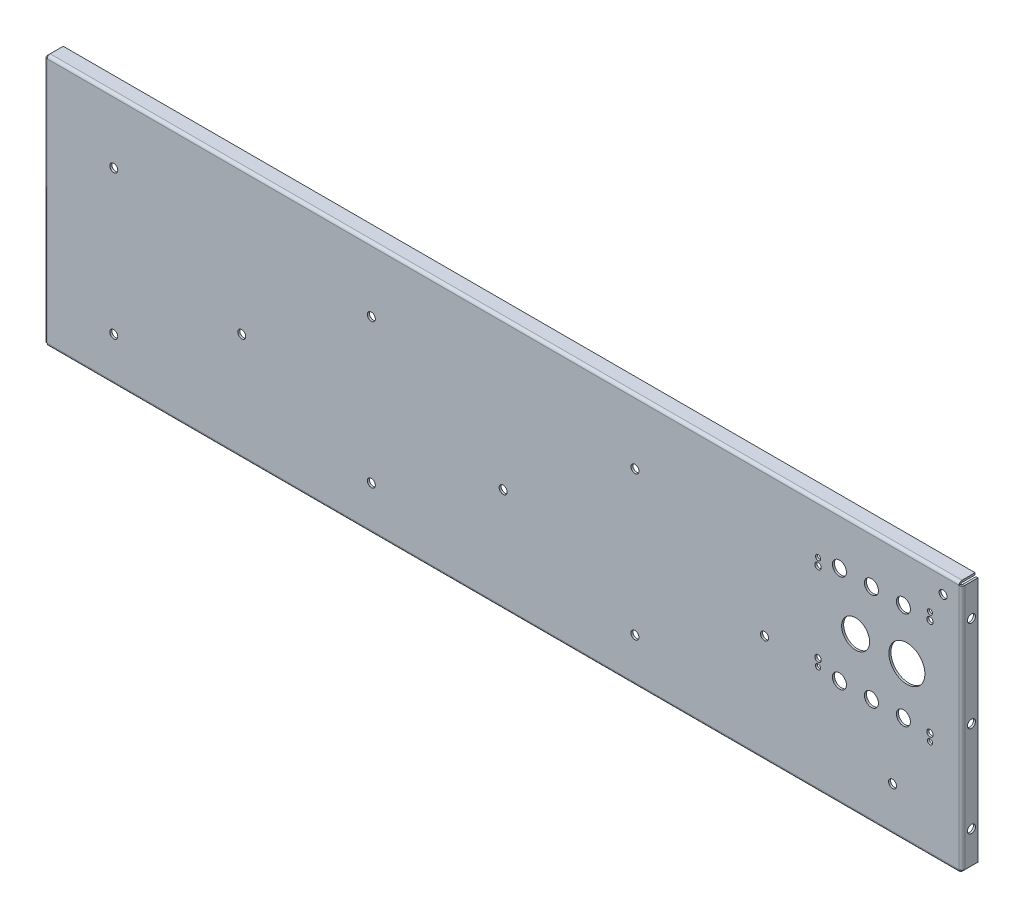
SolidWorks part; units mm, degrees
note: '?' marks a value the reader was unsure of. The reader was unsure of these and kept them because the rebuilt part matched: flange length of "Edge-Flange1", "Edge-Flange2", "Edge-Flange3".
ref_plane "Front Plane" through (0, 0, 0) normal (0, 0, 1) x (1, 0, 0)
ref_plane "Top Plane" through (0, 0, 0) normal (0, 1, 0) x (1, 0, 0)
ref_plane "Right Plane" through (0, 0, 0) normal (1, 0, 0) x (0, 0, -1)
sketch "Sketch1" plane through (0, 0, 0) normal (0, 0, 1) x (1, 0, 0)
  line L1 (-361.95, -100.076) -> (361.95, -100.076)
  line L2 (-361.95, -100.076) -> (-361.95, 100.076)
  line L3 (-361.95, 100.076) -> (361.95, 100.076)
  line L4 (361.95, -100.076) -> (361.95, 100.076)
  line L5 (-361.95, -100.076) -> (361.95, 100.076) construction
  line L6 (-361.95, 100.076) -> (361.95, -100.076) construction
  point P0 (0, 0)
  dimension "D1" = 200.152
  dimension "D2" = 723.9
base flange "Base-Flange1" sketch "Sketch1" thickness 1.6002 reverse thickness direction no parameters "D1"=0.7366
edge flange "Edge-Flange1" sketch "Sketch8" flange angle 90 flange length 12.7 flange position material inside bend radius 0.7366 thickness 1.6002 relief rectangular parameters "D6"=10
sketch "Sketch8" plane through (0, 100.076, -1.6002) normal (0, -1, 0) x (-1, 0, 0)
  line L1 (361.95, 0) -> (-361.95, 0) construction
  line L2 (-361.95, 0) -> (-361.95, 11.0998)
  line L3 (-361.95, 11.0998) -> (361.95, 11.0998)
  line L4 (361.95, 11.0998) -> (361.95, 0)
  line L5 (361.95, 0) -> (-361.95, 0)
bend "EdgeBend1" bend radius 0.7366 bend angle 90 parameters "D5"=1
edge flange "Edge-Flange2" sketch "Sketch11" flange angle 90 flange length 12.7 flange position material inside bend radius 0.7366 thickness 1.6002 relief rectangular parameters "D6"=10
sketch "Sketch11" plane through (0, -100.076, -1.6002) normal (0, -1, 0) x (-1, 0, 0)
  line L1 (361.95, 0) -> (-361.95, 0) construction
  line L2 (-361.95, 0) -> (-361.95, 11.0998)
  line L3 (-361.95, 11.0998) -> (361.95, 11.0998)
  line L4 (361.95, 11.0998) -> (361.95, 0)
  line L6 (361.95, 0) -> (-361.95, 0)
bend "EdgeBend2" bend radius 0.7366 bend angle 90 parameters "D5"=2
sketch "Sketch12" plane through (0, 0, -1.6002) normal (0, 0, -1) x (-1, 0, 0)
  line L0 (-320.548, 23.2684) -> (-361.95, 23.2684) construction
  line L1 (-361.95, -97.7392) -> (-361.95, 97.7392) construction
  line L2 (-320.548, 23.2684) -> (-207.518, -14.351) construction
  circle A0 centre (-207.518, -14.351) radius 3.175
  circle A1 centre (0, -17.526) radius 3.175
  circle A2 centre (207.518, -14.351) radius 3.175
  circle A3 centre (-207.518, -14.351) radius 3.175 construction
  circle A4 centre (-320.548, 23.2684) radius 20.955 construction
  circle A5 centre (-320.548, 23.2684) radius 14.2875
  circle A21 centre (-207.518, -14.351) radius 101.6 construction
  circle A22 centre (0, -17.526) radius 101.6 construction
  circle A23 centre (207.518, -14.351) radius 101.6 construction
  dimension "D1" = 41.91
  dimension "D24" = 203.2
  dimension "D3" = 28.575
  dimension "D4" = 41.402
  dimension "D5" = 119.126
extrude "Cut-Extrude1" cut sketch "Sketch12" against normal through all normal cut yes
sketch "Sketch13" plane through (0, 0, -108.3564) normal (0, 0, -1) x (-1, 0, 0)
  circle A1 centre (-309.118, -65.151) radius 3.175
  circle A2 centre (-104.6381, -65.151) radius 3.175
  circle A3 centre (-104.6381, 49.149) radius 3.175
  circle A4 centre (104.6381, 49.149) radius 3.175
  circle A5 centre (104.6381, -65.151) radius 3.175
  circle A6 centre (309.118, -65.151) radius 3.175
  circle A7 centre (309.118, 49.149) radius 3.175
extrude "Cut-Extrude2" cut sketch "Sketch13" against normal through all normal cut yes
edge flange "Edge-Flange3" sketch "Sketch18" flange profiles "Sketch18", "Sketch19" flange angle 90 flange length 12.7 flange position bend outside bend radius 0.7366 thickness 1.6002 relief rectangular parameters "D6"=10, "D8"=0.254
sketch "Sketch18" plane through (-361.95, 0, -1.6002) normal (-1, 0, 0) x (0, 1, 0)
  line L1 (97.7392, 0) -> (-97.7392, 0) construction
  line L2 (-97.7392, 0) -> (-97.7392, 11.0998)
  line L3 (-97.7392, 11.0998) -> (97.7392, 11.0998)
  line L4 (97.7392, 11.0998) -> (97.7392, 0)
  line L5 (97.7392, 0) -> (-97.7392, 0)
sketch "Sketch19" plane through (361.95, 0, -1.6002) normal (1, 0, 0) x (0, -1, 0)
  line L2 (-97.7392, 0) -> (-97.7392, 11.0998)
  line L3 (-97.7392, 11.0998) -> (97.7392, 11.0998)
  line L4 (97.7392, 11.0998) -> (97.7392, 0)
  line L5 (97.7392, 0) -> (-97.7392, 0) construction
  line L6 (97.7392, 0) -> (-97.7392, 0)
bend "EdgeBend3" bend radius 0.7366 bend angle 90 parameters "D5"=3
bend "EdgeBend4" bend radius 0.7366 bend angle 90 parameters "D5"=4
sketch "Sketch20" plane through (-364.2868, 0, 0) normal (-1, 0, 0) x (0, 0, 1)
  line L1 (-7.5184, 97.7392) -> (-7.5184, -97.7392) construction
  line L2 (-2.3368, 97.7392) -> (-12.7, 97.7392) construction
  line L3 (-12.7, -97.7392) -> (-2.3368, -97.7392) construction
  circle A0 centre (-7.5184, 72.3392) radius 3.175
  circle A1 centre (-7.5184, 0) radius 3.175
  circle A2 centre (-7.5184, -72.3392) radius 3.175
  point P14 (-7.5184, 0)
  dimension "D1" = 6.35
  dimension "D2" = 25.4
  dimension "D3" = 25.4
extrude "Cut-Extrude3" cut sketch "Sketch20" against normal through all normal cut yes
sketch "Sketch22" plane through (0, 0, 0) normal (0, 0, 1) x (1, 0, 0)
  line L0 (279.8318, 23.2684) -> (320.548, 23.2684) construction
  line L1 (338.8601, -21.3086) -> (338.8601, -15.4666) construction
  line L2 (338.8601, 62.0034) -> (338.8601, 67.8454) construction
  line L3 (320.548, 23.2684) -> (338.8601, 62.0034) construction
  line L4 (320.548, 23.2684) -> (338.8601, -15.4666) construction
  line L5 (320.548, 23.2684) -> (317.7781, -15.4666) construction
  line L6 (320.548, 23.2684) -> (317.7781, 62.0034) construction
  line L7 (279.8318, 23.2684) -> (292.3781, 62.0034) construction
  line L8 (279.8318, 23.2684) -> (266.9781, 62.0034) construction
  line L9 (279.8318, 23.2684) -> (266.9781, -15.4666) construction
  line L10 (279.8318, 23.2684) -> (292.3781, -15.4666) construction
  line L11 (279.8318, 23.2684) -> (249.9601, -8.4816) construction
  line L12 (249.9601, -14.3236) -> (249.9601, -8.4816) construction
  line L13 (279.8318, 23.2684) -> (249.9601, 55.0184) construction
  line L14 (249.9601, 55.0184) -> (249.9601, 60.8604) construction
  circle A0 centre (279.8318, 23.2684) radius 21 construction
  circle A1 centre (266.9781, -15.4666) radius 5.5562
  circle A2 centre (249.9601, -8.4816) radius 2.5527
  circle A3 centre (249.9601, -14.3236) radius 2.0447
  circle A4 centre (249.9601, 55.0184) radius 2.5527
  circle A5 centre (249.9601, 60.8604) radius 2.0447
  circle A6 centre (266.9781, 62.0034) radius 5.5562
  circle A7 centre (292.3781, 62.0034) radius 5.5563
  circle A8 centre (317.7781, 62.0034) radius 5.5563
  circle A9 centre (338.8601, 62.0034) radius 2.5527
  circle A10 centre (338.8601, 67.8454) radius 2.0447
  circle A11 centre (338.8601, -15.4666) radius 2.5527
  circle A12 centre (338.8601, -21.3086) radius 2.0447
  circle A13 centre (320.548, 23.2684) radius 14.2812 construction
  circle A14 centre (279.8318, 23.2684) radius 11.1061
  circle A15 centre (292.3781, -15.4666) radius 5.5562
  circle A16 centre (317.7781, -15.4666) radius 5.5562
  circle A17 centre (320.548, 23.2684) radius 21 construction
  circle A18 centre (320.548, 23.2684) radius 14.2875 construction
  point P0 (203.3448, 316.475)
  dimension "D15" = 11.1125
  dimension "D17" = 4.0894
  dimension "D19" = 28.5623
  dimension "D1" = 43.5934
  dimension "D2" = 46.746
  dimension "D3" = 5.842
  dimension "D4" = 136.746
  dimension "D5" = 46.746
  dimension "D6" = 24.896
  dimension "D7" = 36.305
  dimension "D8" = 36.305
  dimension "D9" = 24.896
  dimension "D10" = 40.812
  dimension "D11" = 85.91
  dimension "D12" = 85.91
  dimension "D13" = 29.393
  dimension "D14" = 29.393
  dimension "D16" = 38.8339
  dimension "D18" = 5.842
  dimension "D20" = 154.697
  dimension "D21" = 154.697
  dimension "D22" = 136.746
  dimension "D23" = 40.7162
  dimension "D24" = 42.8454
  dimension "D25" = 40.7162
extrude "Cut-Extrude4" cut sketch "Sketch22" against normal through all normal cut yes
sketch "Sketch23" plane through (0, 0, -1.6002) normal (0, 0, -1) x (-1, 0, 0)
  line L5 (-361.95, 97.7392) -> (361.95, 97.7392) construction
  line L6 (-361.95, -97.7392) -> (-361.95, 97.7392) construction
  circle A0 centre (-349.25, 85.0392) radius 3.175
  dimension "D1" = 6.35
  dimension "D2" = 12.7
  dimension "D3" = 12.7
extrude "Cut-Extrude5" cut sketch "Sketch23" against normal through all normal cut yes
sketch "Bend-Lines1" [suppressed] plane through (0, 0, 0) normal (0, 1, 0) x (1, 0, 0)
sketch "Bounding-Box1" [suppressed] plane through (0, 0, 0) normal (0, 1, 0) x (1, 0, 0)
ref_axis "Axis1" [suppressed] through (400.7155, 0, 0) along (-1, 0, 0)?
sheet metal parameters "Sheet-Metal1" thickness 1.6002 parameters "D1"=0.7366
flat pattern "Flat-Pattern1" [suppressed]
sketch "Bend-Lines2" plane through (0, 0, 0) normal (0, 1, 0) x (1, 0, 0)
sketch3d "Bounding-Box2" [suppressed]
  line L0 (368.3, -100.076, 0) -> (-368.3, -100.076, 0) construction
  line L1 (368.3, 100.076, 0) -> (-368.3, 100.076, 0) construction
  line L2 (368.3, -100.076, 0) -> (368.3, 100.076, 0) construction
  line L3 (-368.3, -100.076, 0) -> (-368.3, 100.076, 0) construction
sheet metal parameters "Sheet-Metal2" thickness 1.6002 parameters "D1"=0.7366
flat pattern "Flat-Pattern1"
sketch "Bend-Lines2" plane through (0, 0, 0) normal (0, 0, 1) x (1, 0, 0)
  line L0 (368.3, 98.9461) -> (-368.3, 98.9461) construction
  line L1 (368.3, 98.9461) -> (-368.3, 98.9461) construction
sketch3d "Bounding-Box2" [suppressed]
  line L0 (-368.3, -100.076, 0) -> (368.3, -100.076, 0) construction
  line L1 (-368.3, 158.5222, 0) -> (368.3, 158.5222, 0) construction
  line L2 (-368.3, -100.076, 0) -> (-368.3, 158.5222, 0) construction
  line L3 (368.3, -100.076, 0) -> (368.3, 158.5222, 0) construction
bend of the flat pattern "Flatten-<EdgeBend1>1"
sheet metal parameters "Sheet-Metal3" thickness 1.6002 parameters "D1"=0.7366
flat pattern "Flat-Pattern1"
sketch "Bend-Lines2" plane through (0, 0, 0) normal (0, 0, 1) x (1, 0, 0)
  line L0 (368.3, 98.9461) -> (-368.3, 98.9461) construction
  line L1 (368.3, 98.9461) -> (-368.3, 98.9461) construction
  line L2 (-368.3, -98.9461) -> (368.3, -98.9461) construction
  line L3 (-368.3, -98.9461) -> (368.3, -98.9461) construction
sketch3d "Bounding-Box2" [suppressed]
  line L0 (-368.3, -110.5162, 0) -> (368.3, -110.5162, 0) construction
  line L1 (-368.3, 110.5162, 0) -> (368.3, 110.5162, 0) construction
  line L2 (-368.3, -110.5162, 0) -> (-368.3, 110.5162, 0) construction
  line L3 (368.3, -110.5162, 0) -> (368.3, 110.5162, 0) construction
bend of the flat pattern "Flatten-<EdgeBend1>1"
bend of the flat pattern "Flatten-<EdgeBend2>1"
sheet metal parameters "Sheet-Metal4" thickness 1.6002 parameters "D1"=0.7366
flat pattern "Flat-Pattern1"
sketch "Bend-Lines2" plane through (0, 0, 0) normal (0, 0, 1) x (1, 0, 0)
  line L0 (368.3, 98.9461) -> (-368.3, 98.9461) construction
  line L1 (368.3, 98.9461) -> (-368.3, 98.9461) construction
  line L2 (-368.3, -98.9461) -> (368.3, -98.9461) construction
  line L3 (-368.3, -98.9461) -> (368.3, -98.9461) construction
sketch3d "Bounding-Box2" [suppressed]
  line L0 (-368.3, -110.5162, 0) -> (368.3, -110.5162, 0) construction
  line L1 (-368.3, 110.5162, 0) -> (368.3, 110.5162, 0) construction
  line L2 (-368.3, -110.5162, 0) -> (-368.3, 110.5162, 0) construction
  line L3 (368.3, -110.5162, 0) -> (368.3, 110.5162, 0) construction
bend of the flat pattern "Flatten-<EdgeBend1>1"
bend of the flat pattern "Flatten-<EdgeBend2>1"
sheet metal parameters "Sheet-Metal5" thickness 1.6002 parameters "D1"=0.7366
flat pattern "Flat-Pattern1"
sketch "Bend-Lines2" plane through (0, 0, 0) normal (0, 0, 1) x (1, 0, 0)
  line L0 (368.3, 98.9461) -> (-368.3, 98.9461) construction
  line L1 (368.3, 98.9461) -> (-368.3, 98.9461) construction
  line L2 (-368.3, -98.9461) -> (368.3, -98.9461) construction
  line L3 (-368.3, -98.9461) -> (368.3, -98.9461) construction
sketch3d "Bounding-Box2" [suppressed]
  line L0 (-368.3, -110.5162, 0) -> (368.3, -110.5162, 0) construction
  line L1 (-368.3, 110.5162, 0) -> (368.3, 110.5162, 0) construction
  line L2 (-368.3, -110.5162, 0) -> (-368.3, 110.5162, 0) construction
  line L3 (368.3, -110.5162, 0) -> (368.3, 110.5162, 0) construction
bend of the flat pattern "Flatten-<EdgeBend1>1"
bend of the flat pattern "Flatten-<EdgeBend2>1"
sheet metal parameters "Sheet-Metal6" thickness 1.6002 parameters "D1"=0.7366
flat pattern "Flat-Pattern1"
sketch "Bend-Lines2" plane through (0, 0, 0) normal (0, 0, 1) x (1, 0, 0)
  line L0 (368.3, 98.9461) -> (-368.3, 98.9461) construction
  line L1 (368.3, 98.9461) -> (-368.3, 98.9461) construction
  line L2 (-368.3, -98.9461) -> (368.3, -98.9461) construction
  line L3 (-368.3, -98.9461) -> (368.3, -98.9461) construction
  line L4 (369.5069, -97.7392) -> (369.5069, 97.7392) construction
  line L5 (-369.5069, 97.7392) -> (-369.5069, -97.7392) construction
  line L6 (369.5069, -97.7392) -> (369.5069, 97.7392) construction
  line L7 (-369.5069, 97.7392) -> (-369.5069, -97.7392) construction
sketch3d "Bounding-Box2" [suppressed]
  line L0 (-381.077, -110.5162, 0) -> (381.077, -110.5162, 0) construction
  line L1 (-381.077, 110.5162, 0) -> (381.077, 110.5162, 0) construction
  line L2 (-381.077, -110.5162, 0) -> (-381.077, 110.5162, 0) construction
  line L3 (381.077, -110.5162, 0) -> (381.077, 110.5162, 0) construction
bend of the flat pattern "Flatten-<EdgeBend1>1"
bend of the flat pattern "Flatten-<EdgeBend2>1"
bend of the flat pattern "Flatten-<EdgeBend3>1"
bend of the flat pattern "Flatten-<EdgeBend4>1"
sheet metal parameters "Sheet-Metal7" thickness 1.6002 parameters "D1"=0.7366
flat pattern "Flat-Pattern1"
sketch "Bend-Lines2" plane through (0, 0, 0) normal (0, 0, 1) x (1, 0, 0)
  line L0 (361.95, 98.9461) -> (-361.95, 98.9461) construction
  line L1 (361.95, 98.9461) -> (-361.95, 98.9461) construction
  line L2 (-361.95, -98.9461) -> (361.95, -98.9461) construction
  line L3 (-361.95, -98.9461) -> (361.95, -98.9461) construction
  line L4 (363.1569, -97.7392) -> (363.1569, 97.7392) construction
  line L5 (-363.1569, 97.7392) -> (-363.1569, -97.7392) construction
  line L6 (363.1569, -97.7392) -> (363.1569, 97.7392) construction
  line L7 (-363.1569, 97.7392) -> (-363.1569, -97.7392) construction
sketch3d "Bounding-Box2" [suppressed]
  line L0 (-374.727, -110.5162, 0) -> (374.727, -110.5162, 0) construction
  line L1 (-374.727, 110.5162, 0) -> (374.727, 110.5162, 0) construction
  line L2 (-374.727, -110.5162, 0) -> (-374.727, 110.5162, 0) construction
  line L3 (374.727, -110.5162, 0) -> (374.727, 110.5162, 0) construction
bend of the flat pattern "Flatten-<EdgeBend1>1"
bend of the flat pattern "Flatten-<EdgeBend2>1"
bend of the flat pattern "Flatten-<EdgeBend3>1"
bend of the flat pattern "Flatten-<EdgeBend4>1"
sheet metal parameters "Sheet-Metal8" thickness 1.6002 parameters "D1"=0.7366
flat pattern "Flat-Pattern1"
sketch "Bend-Lines2" plane through (0, 0, 0) normal (0, 0, 1) x (1, 0, 0)
  line L0 (361.95, 98.9461) -> (-361.95, 98.9461) construction
  line L1 (361.95, 98.9461) -> (-361.95, 98.9461) construction
  line L2 (-361.95, -98.9461) -> (361.95, -98.9461) construction
  line L3 (-361.95, -98.9461) -> (361.95, -98.9461) construction
  line L4 (363.1569, -97.7392) -> (363.1569, 97.7392) construction
  line L5 (-363.1569, 97.7392) -> (-363.1569, -97.7392) construction
  line L6 (363.1569, -97.7392) -> (363.1569, 97.7392) construction
  line L7 (-363.1569, 97.7392) -> (-363.1569, -97.7392) construction
sketch3d "Bounding-Box2" [suppressed]
  line L0 (-374.727, -110.5162, 0) -> (374.727, -110.5162, 0) construction
  line L1 (-374.727, 110.5162, 0) -> (374.727, 110.5162, 0) construction
  line L2 (-374.727, -110.5162, 0) -> (-374.727, 110.5162, 0) construction
  line L3 (374.727, -110.5162, 0) -> (374.727, 110.5162, 0) construction
bend of the flat pattern "Flatten-<EdgeBend1>1"
bend of the flat pattern "Flatten-<EdgeBend2>1"
bend of the flat pattern "Flatten-<EdgeBend3>1"
bend of the flat pattern "Flatten-<EdgeBend4>1"
sheet metal parameters "Sheet-Metal9" thickness 1.6002 parameters "D1"=0.7366
flat pattern "Flat-Pattern1"
sketch "Bend-Lines2" plane through (0, 0, 0) normal (0, 0, 1) x (1, 0, 0)
  line L0 (361.95, 98.9461) -> (-361.95, 98.9461) construction
  line L1 (361.95, 98.9461) -> (-361.95, 98.9461) construction
  line L2 (-361.95, -98.9461) -> (361.95, -98.9461) construction
  line L3 (-361.95, -98.9461) -> (361.95, -98.9461) construction
  line L4 (363.1569, -97.7392) -> (363.1569, 97.7392) construction
  line L5 (-363.1569, 97.7392) -> (-363.1569, -97.7392) construction
  line L6 (363.1569, -97.7392) -> (363.1569, 97.7392) construction
  line L7 (-363.1569, 97.7392) -> (-363.1569, -97.7392) construction
sketch3d "Bounding-Box2" [suppressed]
  line L0 (-374.727, -110.5162, 0) -> (374.727, -110.5162, 0) construction
  line L1 (-374.727, 110.5162, 0) -> (374.727, 110.5162, 0) construction
  line L2 (-374.727, -110.5162, 0) -> (-374.727, 110.5162, 0) construction
  line L3 (374.727, -110.5162, 0) -> (374.727, 110.5162, 0) construction
bend of the flat pattern "Flatten-<EdgeBend1>1"
bend of the flat pattern "Flatten-<EdgeBend2>1"
bend of the flat pattern "Flatten-<EdgeBend3>1"
bend of the flat pattern "Flatten-<EdgeBend4>1"
